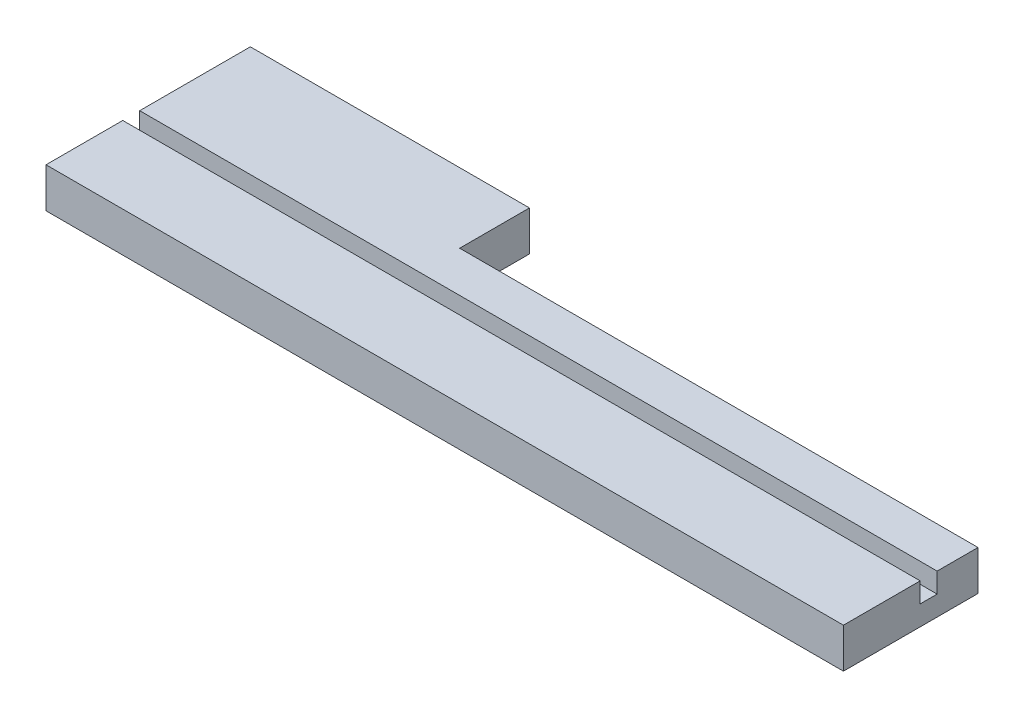
SolidWorks part; units mm, degrees
ref_plane "Front Plane" through (0, 0, 0) normal (0, 0, 1) x (1, 0, 0)
ref_plane "Top Plane" through (0, 0, 0) normal (0, 1, 0) x (1, 0, 0)
ref_plane "Right Plane" through (0, 0, 0) normal (1, 0, 0) x (0, 0, -1)
sketch "Sketch1" plane through (0, 0, 0) normal (0, 1, 0) x (1, 0, 0)
  line L1 (-7.5455, 9.1364) -> (72.4545, 9.1364)
  line L2 (-7.5455, 9.1364) -> (-7.5455, -4.3636)
  line L3 (-7.5455, -4.3636) -> (72.4545, -4.3636)
  line L4 (72.4545, 9.1364) -> (72.4545, -4.3636)
  dimension "D1" = 13.5
  dimension "D2" = 80
extrude "Boss-Extrude1" add sketch "Sketch1" along normal blind 2
sketch "Sketch2" plane through (0, 2, 0) normal (0, 1, 0) x (1, 0, 0)
  line L0 (72.4545, -4.3636) -> (72.4545, 9.1364) construction
  line L1 (-7.5455, -4.3636) -> (72.4545, -4.3636)
  line L2 (-7.5455, -4.3636) -> (-7.5455, 3.3364)
  line L3 (-7.5455, 3.3364) -> (72.4545, 3.3364)
  line L4 (72.4545, -4.3636) -> (72.4545, 3.3364)
  line L7 (-7.5455, 9.1364) -> (72.4545, 9.1364)
  line L8 (-7.5455, 9.1364) -> (-7.5455, 5.0364)
  line L9 (-7.5455, 5.0364) -> (72.4545, 5.0364)
  line L10 (72.4545, 9.1364) -> (72.4545, 5.0364)
  dimension "D1" = 7.7
  dimension "D2" = 1.7
  dimension "D3" = 4.1
extrude "Boss-Extrude2" add sketch "Sketch2" along normal blind 2 contours L3 L4 L1 L2 | L8 L9 L10 L7
sketch "Sketch3" plane through (0, 0, 0) normal (0, -1, 0) x (1, 0, 0)
  line L0 (72.4545, 4.3636) -> (72.4545, -9.1364) construction
  line L1 (-7.5455, -9.1364) -> (20.4545, -9.1364)
  line L2 (-7.5455, -9.1364) -> (-7.5455, -16.1364)
  line L3 (-7.5455, -16.1364) -> (20.4545, -16.1364)
  line L4 (20.4545, -9.1364) -> (20.4545, -16.1364)
  dimension "D1" = 7
  dimension "D2" = 52
extrude "Boss-Extrude3" add sketch "Sketch3" against normal up to surface (4 mm away) up to face at (32.4545, 4, -7.0864)
